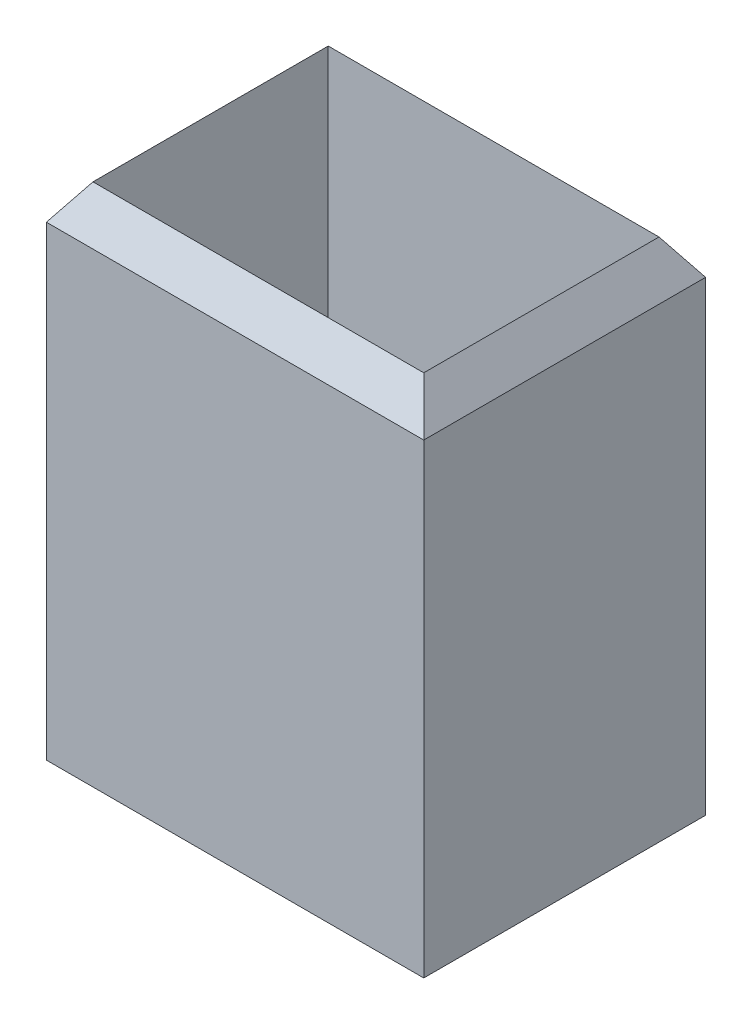
SolidWorks part; units mm, degrees
note: The reader was unsure of these and kept them because the rebuilt part matched: shared geometry of "Sketch2<2>".
ref_plane "Front Plane" through (0, 0, 0) normal (0, 0, 1) x (1, 0, 0)
ref_plane "Top Plane" through (0, 0, 0) normal (0, 1, 0) x (1, 0, 0)
ref_plane "Right Plane" through (0, 0, 0) normal (1, 0, 0) x (0, 0, -1)
sketch "Sketch1" plane through (0, 0, 0) normal (0, 1, 0) x (1, 0, 0)
  line L0 (0, -6.05) -> (0, 6.05) construction
  line L1 (-8.1, -6.05) -> (8.1, -6.05)
  line L2 (-8.1, -6.05) -> (-8.1, 6.05)
  line L3 (-8.1, 6.05) -> (8.1, 6.05)
  line L4 (8.1, -6.05) -> (8.1, 6.05)
  point P5 (0, 0)
  dimension "D1" = 16.2
  dimension "D2" = 12.1
extrude "Boss-Extrude1" add sketch "Sketch1" along normal blind 20
ref_plane "Plane1" through (0, 21.5, 0) normal (0, 1, 0) x (1, 0, 0)
sketch "Sketch2" plane through (0, 21.5, 0) normal (0, 1, 0) x (1, 0, 0)
  line L0 (8.1, 6.05) -> (-8.1, -6.05) construction
  line L5 (-7.1, -5.05) -> (7.1, -5.05)
  line L6 (-7.1, -5.05) -> (-7.1, 5.05)
  line L7 (-7.1, 5.05) -> (7.1, 5.05)
  line L8 (7.1, -5.05) -> (7.1, 5.05)
  line L9 (-7.1, -5.05) -> (7.1, 5.05) construction
  line L10 (-7.1, 5.05) -> (7.1, -5.05) construction
  line L11 (8.1, -6.05) -> (-8.1, 6.05) construction
  line L12 (8.1, -6.05) -> (8.1, 6.05) construction
  line L13 (8.1, 6.05) -> (-8.1, 6.05) construction
  point P0 (0, 0)
  point P14 (0, 0)
  dimension "D1" = 1
  dimension "D2" = 1
loft "Loft1" add profiles "Sketch2" section face at (0, 20, 0) section "Sketch2"
extrude "Cut-Extrude1" cut sketch "Sketch2<2>" against normal through all
sketch "Sketch2<2>" plane through (0, 21.5, 0) normal (0, 1, 0) x (1, 0, 0) same geometry as "Sketch2"
sketch "Sketch5" plane through (0, 0, 6.05) normal (0, 0, 1) x (1, 0, 0)
  line L0 (2.7699, 9.8008) -> (2.7699, 2.9013) construction
  line L1 (3.7699, 9.8008) -> (3.7699, 2.9013)
  line L2 (1.7699, 9.8008) -> (1.7699, 2.9013)
  arc A0 (3.7699, 9.8008) -> (1.7699, 9.8008) centre (2.7699, 9.8008) ccw
  arc A1 (1.7699, 2.9013) -> (3.7699, 2.9013) centre (2.7699, 2.9013) ccw
  point P2 (2.7699, 6.3511)
  dimension "D1" = 2
extrude "Cut-Extrude2" [suppressed] cut sketch "Sketch5" against normal blind 0.2
sketch "Sketch6" plane through (0, 0, 0) normal (0, -1, 0) x (1, 0, 0)
  line L0 (-16.0628, -8.3487) -> (16.0628, -8.3487) construction
  line L2 (-22.5, 8.831) -> (-22.5, -4.4864) construction
  line L3 (22.5, 12.0134) -> (22.5, -1.304) construction
  line L4 (0, -8.3487) -> (0, 0) construction
  arc A0 (16.0628, -8.3487) -> (21.5327, 1.4824) centre (16.0628, -1.9115) ccw construction
  arc A1 (-16.0628, -8.3487) -> (-21.5327, 1.4824) centre (-16.0628, -1.9115) cw construction
  arc A2 (-21.5327, 1.4824) -> (21.5327, 1.4824) centre (0, -11.8779) cw construction
  point P5 (0, -8.3487)
  point P16 (21.5327, 1.4824)
  point P17 (0, -8.3487)
  dimension "D1" = 45
sketch "Sketch7" plane through (0, 0, 0) normal (0, -1, 0) x (1, 0, 0)
  line L1 (0, -8.221) -> (13.5, -8.221)
  line L2 (0, 3.3849) -> (0, -12.0574) construction
  line L4 (0, 8.221) -> (0, 6.05)
  line L5 (-8.1, 6.05) -> (8.1, 6.05) construction
  line L6 (0, 6.05) -> (8.1, 6.05)
  line L7 (21.5, 8.6901) -> (21.5, 4.9158) construction
  line L9 (0, -8.3487) -> (0, 0) construction
  line L11 (8.1, 6.05) -> (8.1, -6.05)
  line L12 (8.1, -6.05) -> (0, -6.05)
  line L13 (8.1, -6.05) -> (-8.1, -6.05) construction
  line L14 (0, -6.05) -> (0, -8.221)
  line L15 (8.1, 8.0679) -> (8.1, -8.221) construction
  arc A0 (13.5, -8.221) -> (14.0232, 7.7619) centre (13.5, -0.221) ccw
  arc A2 (14.0232, 7.7619) -> (0, 8.221) centre (0, -206.2029) ccw
  point P10 (8.1, -7.5537)
  point P21 (8.1, 6.9713)
  point P25 (0, -7.6386)
  point P28 (13.8647, 8.2659)
  point P29 (13.8647, 8.5212)
  point P30 (14.0232, 7.7619)
  dimension "D1" = 13.5
  dimension "D2" = 21.5
